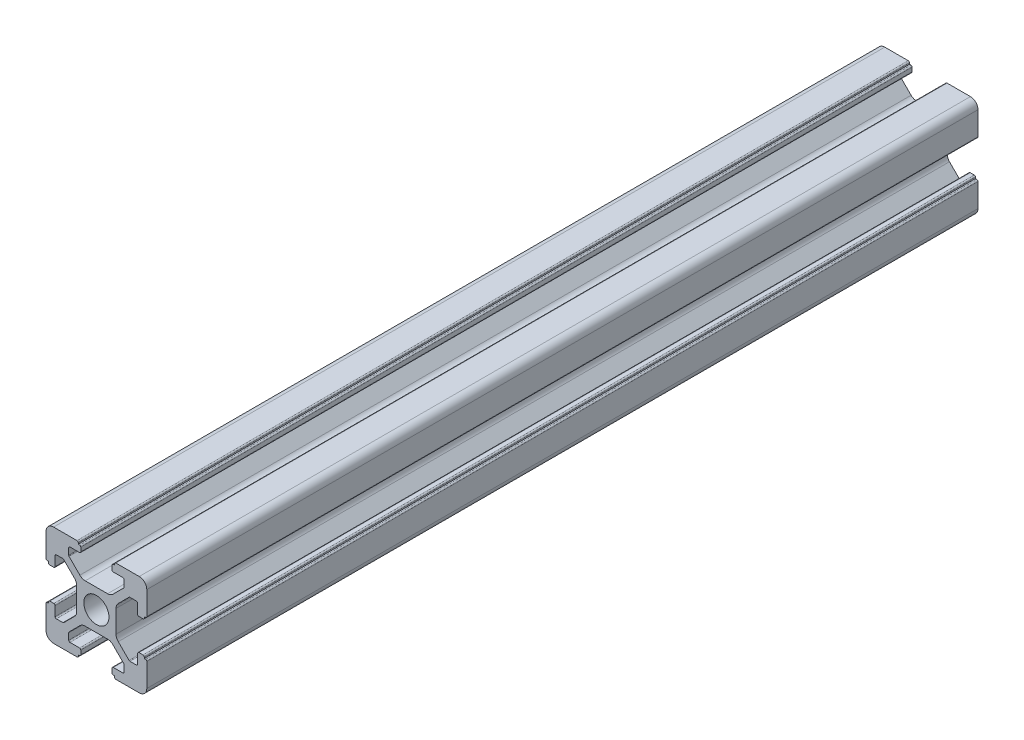
SolidWorks part; units mm, degrees
ref_plane "前视基准面" through (0, 0, 0) normal (0, 0, 1) x (1, 0, 0)
ref_plane "上视基准面" through (0, 0, 0) normal (0, 1, 0) x (1, 0, 0)
ref_plane "右视基准面" through (0, 0, 0) normal (1, 0, 0) x (0, 0, -1)
sketch "草图1" plane through (0, 0, 0) normal (0, 0, 1) x (1, 0, 0)
  line L0 (0, 0) -> (0, 5.5) construction
  line L1 (-8.5023, -10.0023) -> (-3.85, -10.0023)
  line L2 (-10.0023, -8.5023) -> (-10.0023, -3.85)
  line L3 (-8.5023, 10.0023) -> (-3.85, 10.0023)
  line L4 (10.0023, -8.5023) -> (10.0023, -3.85)
  line L5 (-10.0023, -10.0023) -> (10.0023, 10.0023) construction
  line L6 (-10.0023, 10.0023) -> (10.0023, -10.0023) construction
  line L7 (-2.218, -3.9) -> (2.218, -3.9)
  line L8 (-3.9, -2.218) -> (-3.9, 2.218)
  line L9 (-2.218, 3.9) -> (2.218, 3.9)
  line L10 (3.9, -2.218) -> (3.9, 2.218)
  line L11 (-3.9, -3.9) -> (3.9, 3.9) construction
  line L12 (-3.9, 3.9) -> (3.9, -3.9) construction
  line L13 (-5.25, -8.2) -> (-3.35, -8.2)
  line L14 (-8.2, -5.25) -> (-8.2, -3.35)
  line L15 (-5.25, 8.2) -> (-3.35, 8.2)
  line L16 (8.2, -5.25) -> (8.2, -3.35)
  line L17 (-8.2, -8.2) -> (8.2, 8.2) construction
  line L18 (-8.2, 8.2) -> (8.2, -8.2) construction
  line L19 (-7.95, 5.5) -> (-6.6642, 5.5)
  line L20 (0, 0) -> (5.5, 0) construction
  line L23 (-5.5, 7.95) -> (-5.5, 6.6642)
  line L26 (0, 0) -> (-0.5303, 0.5303)
  line L27 (3.2787, 4.3393) -> (5.4268, 6.4874)
  line L28 (0, 0) -> (0.5303, -0.5303)
  line L29 (5.5, 6.6642) -> (5.5, 7.95)
  line L30 (4.3393, 3.2787) -> (6.4874, 5.4268)
  line L31 (6.6642, 5.5) -> (7.95, 5.5)
  line L32 (4.3393, -3.2787) -> (6.4874, -5.4268)
  line L33 (3.2787, -4.3393) -> (5.4268, -6.4874)
  line L34 (-3.2787, -4.3393) -> (-5.4268, -6.4874)
  line L35 (-4.3393, -3.2787) -> (-6.4874, -5.4268)
  line L36 (-4.3393, 3.2787) -> (-6.4874, 5.4268)
  line L37 (-3.2787, 4.3393) -> (-5.4268, 6.4874)
  line L38 (3.1, -8.45) -> (3.1, -9.2523)
  line L39 (8.45, 3.1) -> (9.2523, 3.1)
  line L40 (-5.5, -6.6642) -> (-5.5, -7.95)
  line L41 (-6.6642, -5.5) -> (-7.95, -5.5)
  line L42 (5.5, -6.6642) -> (5.5, -7.95)
  line L43 (6.6642, -5.5) -> (7.95, -5.5)
  line L44 (9.2523, -3.1) -> (8.45, -3.1)
  line L46 (10.0023, 3.85) -> (10.0023, 8.5023)
  line L47 (8.2, 3.35) -> (8.2, 5.25)
  line L48 (-3.1, -9.2523) -> (-3.1, -8.45)
  line L49 (-8.45, -3.1) -> (-9.2523, -3.1)
  line L50 (-9.2523, 3.1) -> (-8.45, 3.1)
  line L51 (-3.1, 8.45) -> (-3.1, 9.2523)
  line L52 (3.1, 9.2523) -> (3.1, 8.45)
  line L53 (3.85, 10.0023) -> (8.5023, 10.0023)
  line L54 (3.35, 8.2) -> (5.25, 8.2)
  line L55 (-10.0023, 3.85) -> (-10.0023, 8.5023)
  line L56 (-8.2, 3.35) -> (-8.2, 5.25)
  line L57 (3.35, -8.2) -> (5.25, -8.2)
  line L58 (3.85, -10.0023) -> (8.5023, -10.0023)
  line L59 (9.7523, -3.6) -> (9.5023, -3.6)
  line L61 (9.7523, 3.6) -> (9.5023, 3.6)
  line L62 (9.5023, -3.6) -> (9.5023, -3.35)
  line L63 (3.6, -9.7523) -> (3.6, -9.5023)
  line L64 (3.35, -9.5023) -> (3.6, -9.5023)
  line L65 (9.5023, 3.35) -> (9.5023, 3.6)
  line L66 (-3.6, -9.5023) -> (-3.35, -9.5023)
  line L67 (-3.6, -9.7523) -> (-3.6, -9.5023)
  line L68 (-9.7523, -3.6) -> (-9.5023, -3.6)
  line L69 (-9.5023, -3.35) -> (-9.5023, -3.6)
  line L70 (-9.5023, 3.6) -> (-9.5023, 3.35)
  line L71 (-9.7523, 3.6) -> (-9.5023, 3.6)
  line L72 (-3.6, 9.7523) -> (-3.6, 9.5023)
  line L73 (-3.35, 9.5023) -> (-3.6, 9.5023)
  line L74 (3.6, 9.5023) -> (3.35, 9.5023)
  line L75 (3.6, 9.7523) -> (3.6, 9.5023)
  circle A0 centre (0, 0) radius 2.5
  arc A1 (10.0023, 8.5023) -> (8.5023, 10.0023) centre (8.5023, 8.5023) ccw
  arc A2 (8.5023, -10.0023) -> (10.0023, -8.5023) centre (8.5023, -8.5023) ccw
  arc A3 (-10.0023, -8.5023) -> (-8.5023, -10.0023) centre (-8.5023, -8.5023) ccw
  arc A4 (-10.0023, 8.5023) -> (-8.5023, 10.0023) centre (-8.5023, 8.5023) cw
  arc A5 (-9.5023, -3.35) -> (-9.2523, -3.1) centre (-9.2523, -3.35) cw
  arc A6 (-9.7523, -3.6) -> (-10.0023, -3.85) centre (-9.7523, -3.85) ccw
  arc A7 (-8.45, -3.1) -> (-8.2, -3.35) centre (-8.45, -3.35) cw
  arc A8 (-7.95, -5.5) -> (-8.2, -5.25) centre (-7.95, -5.25) cw
  arc A9 (-6.4874, -5.4268) -> (-6.6642, -5.5) centre (-6.6642, -5.25) cw
  arc A10 (-5.4268, -6.4874) -> (-5.5, -6.6642) centre (-5.25, -6.6642) ccw
  arc A11 (-5.5, -7.95) -> (-5.25, -8.2) centre (-5.25, -7.95) ccw
  arc A12 (-3.6, -9.7523) -> (-3.85, -10.0023) centre (-3.85, -9.7523) cw
  arc A13 (-3.35, -9.5023) -> (-3.1, -9.2523) centre (-3.35, -9.2523) ccw
  arc A14 (-3.1, -8.45) -> (-3.35, -8.2) centre (-3.35, -8.45) ccw
  arc A15 (3.1, -8.45) -> (3.35, -8.2) centre (3.35, -8.45) cw
  arc A16 (5.5, -7.95) -> (5.25, -8.2) centre (5.25, -7.95) cw
  arc A17 (5.4268, -6.4874) -> (5.5, -6.6642) centre (5.25, -6.6642) cw
  arc A18 (6.4874, -5.4268) -> (6.6642, -5.5) centre (6.6642, -5.25) ccw
  arc A19 (7.95, -5.5) -> (8.2, -5.25) centre (7.95, -5.25) ccw
  arc A20 (8.45, -3.1) -> (8.2, -3.35) centre (8.45, -3.35) ccw
  arc A21 (9.5023, -3.35) -> (9.2523, -3.1) centre (9.2523, -3.35) ccw
  arc A22 (9.7523, -3.6) -> (10.0023, -3.85) centre (9.7523, -3.85) cw
  arc A23 (3.35, -9.5023) -> (3.1, -9.2523) centre (3.35, -9.2523) cw
  arc A24 (3.6, -9.7523) -> (3.85, -10.0023) centre (3.85, -9.7523) ccw
  arc A25 (7.95, 5.5) -> (8.2, 5.25) centre (7.95, 5.25) cw
  arc A26 (8.2, 3.35) -> (8.45, 3.1) centre (8.45, 3.35) ccw
  arc A27 (9.5023, 3.35) -> (9.2523, 3.1) centre (9.2523, 3.35) cw
  arc A28 (9.7523, 3.6) -> (10.0023, 3.85) centre (9.7523, 3.85) ccw
  arc A29 (6.6642, 5.5) -> (6.4874, 5.4268) centre (6.6642, 5.25) ccw
  arc A30 (5.4268, 6.4874) -> (5.5, 6.6642) centre (5.25, 6.6642) ccw
  arc A31 (5.5, 7.95) -> (5.25, 8.2) centre (5.25, 7.95) ccw
  arc A32 (3.1, 8.45) -> (3.35, 8.2) centre (3.35, 8.45) ccw
  arc A33 (3.6, 9.7523) -> (3.85, 10.0023) centre (3.85, 9.7523) cw
  arc A34 (3.35, 9.5023) -> (3.1, 9.2523) centre (3.35, 9.2523) ccw
  arc A35 (-9.7523, 3.6) -> (-10.0023, 3.85) centre (-9.7523, 3.85) cw
  arc A36 (-9.5023, 3.35) -> (-9.2523, 3.1) centre (-9.2523, 3.35) ccw
  arc A37 (-8.45, 3.1) -> (-8.2, 3.35) centre (-8.45, 3.35) ccw
  arc A38 (-8.2, 5.25) -> (-7.95, 5.5) centre (-7.95, 5.25) cw
  arc A39 (-6.4874, 5.4268) -> (-6.6642, 5.5) centre (-6.6642, 5.25) ccw
  arc A40 (-5.4268, 6.4874) -> (-5.5, 6.6642) centre (-5.25, 6.6642) cw
  arc A41 (-5.5, 7.95) -> (-5.25, 8.2) centre (-5.25, 7.95) cw
  arc A42 (-3.1, 8.45) -> (-3.35, 8.2) centre (-3.35, 8.45) cw
  arc A43 (-3.1, 9.2523) -> (-3.35, 9.5023) centre (-3.35, 9.2523) ccw
  arc A44 (-3.6, 9.7523) -> (-3.85, 10.0023) centre (-3.85, 9.7523) ccw
  arc A45 (-4.3393, 3.2787) -> (-3.9, 2.218) centre (-5.4, 2.218) cw
  arc A46 (-3.2787, 4.3393) -> (-2.218, 3.9) centre (-2.218, 5.4) ccw
  arc A47 (3.2787, 4.3393) -> (2.218, 3.9) centre (2.218, 5.4) cw
  arc A48 (4.3393, 3.2787) -> (3.9, 2.218) centre (5.4, 2.218) ccw
  arc A49 (4.3393, -3.2787) -> (3.9, -2.218) centre (5.4, -2.218) cw
  arc A50 (3.2787, -4.3393) -> (2.218, -3.9) centre (2.218, -5.4) ccw
  arc A51 (-4.3393, -3.2787) -> (-3.9, -2.218) centre (-5.4, -2.218) ccw
  arc A52 (-2.218, -3.9) -> (-3.2787, -4.3393) centre (-2.218, -5.4) ccw
  point P0 (0, 0)
  point P7 (10.0023, 0)
  point P62 (0, 0)
  point P76 (0, 0)
  point P92 (-8.2, -5.5)
  point P99 (0, 0)
  point P106 (-5.5, -8.2)
  point P117 (5.5, -8.2)
  point P124 (8.2, -5.5)
  point P137 (8.2, 5.5)
  point P140 (8.2, 3.1)
  point P147 (6.5607, 5.5)
  point P152 (5.5, 8.2)
  point P167 (-8.2, 5.5)
  point P174 (-5.5, 8.2)
  dimension "D1" = 1.5
  dimension "D5" = 0.25
  dimension "D6" = 1.5
  dimension "D2" = 4
  dimension "D3" = 4
  dimension "D4" = 4
extrude "凸台-拉伸1" add sketch "草图1" along normal blind 165 contours A52 L7 A50 L33 A17 L42 A16 L57 A15 L38 A23 L64 L63 A24 L58 A2 L4 A22 L59 L62 A21 L44 A20 L16 A19 L43 A18 L32 A49 L10 A48 L30 A29 L31 A25 L47 A26 L39 A27 L65 L61 A28 L46 A1 L53 A33 L75 L74 A34 L52 A32 region at (-9.3629, -9.3629, 0)
